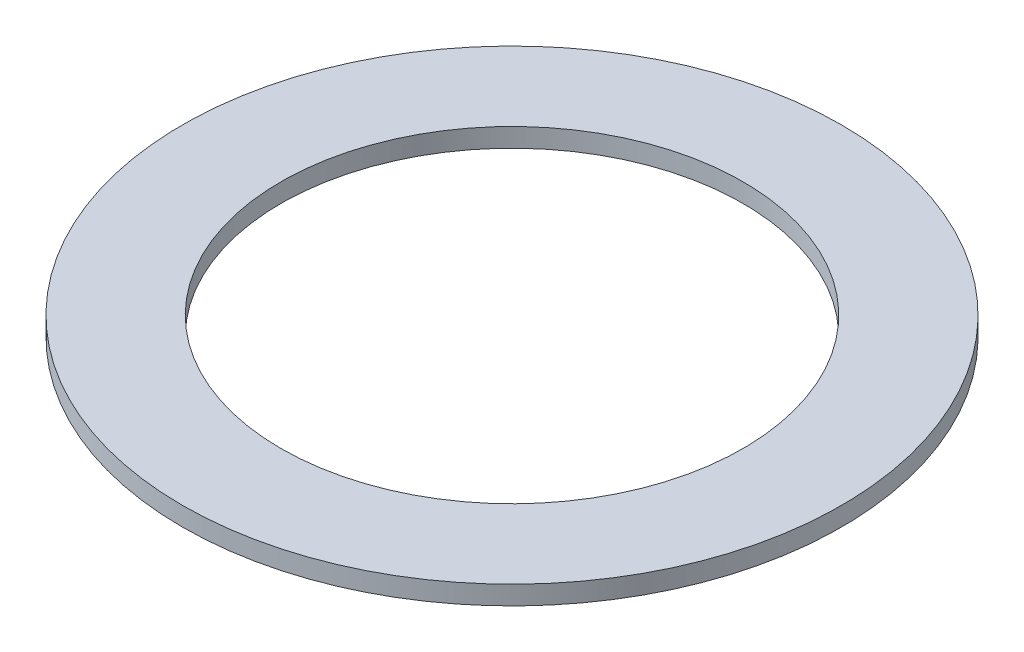
SolidWorks part; units mm, degrees
ref_plane "Front Plane" through (0, 0, 0) normal (0, 0, 1) x (1, 0, 0)
ref_plane "Top Plane" through (0, 0, 0) normal (0, 1, 0) x (1, 0, 0)
ref_plane "Right Plane" through (0, 0, 0) normal (1, 0, 0) x (0, 0, -1)
sketch "Sketch1" plane through (0, 0, 0) normal (0, 1, 0) x (1, 0, 0)
  circle A0 centre (0, 0) radius 12.27
  circle A1 centre (0, 0) radius 17.5
  dimension "D1" = 24.54
  dimension "D2" = 35
extrude "Boss-Extrude1" add sketch "Sketch1" along normal blind 1
